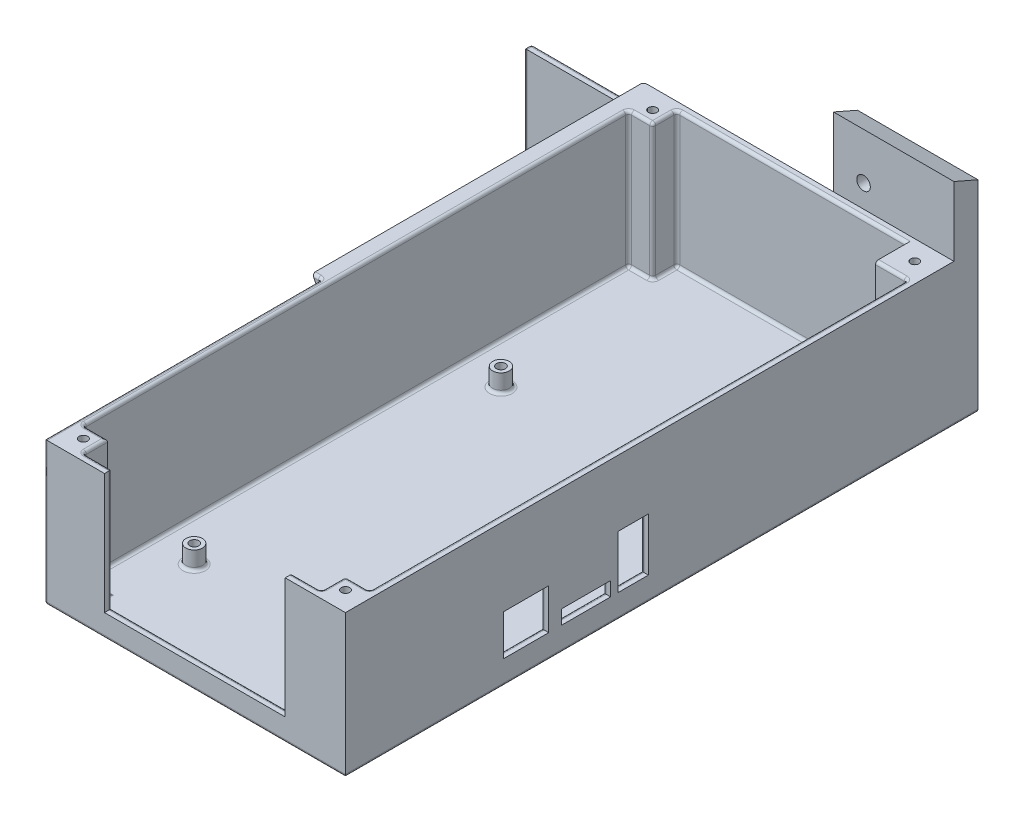
SolidWorks part; units mm, degrees
ref_plane "Front Plane" through (0, 0, 0) normal (0, 0, 1) x (1, 0, 0)
ref_plane "Top Plane" through (0, 0, 0) normal (0, 1, 0) x (1, 0, 0)
ref_plane "Right Plane" through (0, 0, 0) normal (1, 0, 0) x (0, 0, -1)
sketch "Sketch1" plane through (0, 0, 0) normal (0, 1, 0) x (1, 0, 0)
  line L0 (0, 0) -> (100, 0)
  line L2 (100, 210) -> (60, 210)
  line L3 (60, 210) -> (60, 202)
  line L4 (60, 202) -> (-40.25, 202)
  line L5 (-40.25, 202) -> (-40.25, 199.5)
  line L6 (-40.25, 199.5) -> (0, 199.5)
  line L7 (0, 199.5) -> (0, 0)
  line L8 (100, 210) -> (100, 202)
  line L14 (100, 202) -> (100, 0)
  point P11 (100, 200.922)
  dimension "D1" = 100
  dimension "D2" = 210
  dimension "D3" = 40
  dimension "D4" = 100.25
  dimension "D5" = 40.25
  dimension "D6" = 2.5
  dimension "D7" = 199.5
  dimension "D8" = 8
extrude "Boss-Extrude1" add sketch "Sketch1" along normal blind 47.5
sketch "Sketch2" plane through (0, 0, 0) normal (0, 1, 0) x (1, 0, 0)
  line L0 (2.5, 10.5) -> (10.5, 10.5)
  line L1 (10.5, 10.5) -> (10.5, 2.5)
  line L2 (10.5, 2.5) -> (89.5, 2.5)
  line L3 (89.5, 2.5) -> (89.5, 10.5)
  line L4 (89.5, 10.5) -> (97.5, 10.5)
  line L9 (10.5, 199.5) -> (10.5, 191.5)
  line L10 (10.5, 191.5) -> (2.5, 191.5)
  line L11 (2.5, 191.5) -> (2.5, 10.5)
  line L12 (0, 199.5) -> (0, 0) construction
  line L13 (60, 202) -> (-40.25, 202) construction
  line L15 (97.5, 189) -> (87, 189)
  line L16 (0, 0) -> (100, 0) construction
  line L17 (97.5, 10.5) -> (97.5, 189)
  line L22 (87, 189) -> (87, 199.5)
  line L24 (100, 0) -> (100, 210) construction
  line L25 (87, 199.5) -> (10.5, 199.5)
  dimension "D1" = 2.5
  dimension "D2" = 10.5
  dimension "D3" = 10.5
  dimension "D4" = 10.5
  dimension "D5" = 2.5
  dimension "D6" = 10.5
  dimension "D8" = 10.5
  dimension "D9" = 10.5
  dimension "D10" = 10.5
  dimension "D11" = 2.5
extrude "Cut-Extrude1" cut sketch "Sketch2" along normal blind 45 from offset 2.5
sketch "Sketch5" plane through (0, 47.5, 0) normal (0, 1, 0) x (1, 0, 0)
  line L1 (100, 210) -> (60, 210) construction
  line L2 (0, 0) -> (100, 0) construction
  line L3 (0, 199.5) -> (0, 0) construction
  line L4 (60, 202) -> (-40.25, 202) construction
  line L5 (100, 0) -> (100, 210) construction
  circle A0 centre (93.5, 195.5) radius 1.4
  circle A1 centre (93.5, 6.5) radius 1.4
  circle A2 centre (6.5, 6.5) radius 1.4
  circle A3 centre (6.5, 195.5) radius 1.4
  dimension "D1" = 2.8
  dimension "D4" = 2.8
  dimension "D9" = 2.8
  dimension "D2" = 2.8
  dimension "D3" = 14.5
  dimension "D5" = 6.5
  dimension "D6" = 6.5
  dimension "D7" = 6.5
  dimension "D8" = 6.5
  dimension "D10" = 6.5
  dimension "D11" = 6.5
extrude "Cut-Extrude2" cut sketch "Sketch5" against normal blind 10
sketch "Sketch6" plane through (0, 0, 0) normal (0, 0, 1) x (1, 0, 0)
  line L0 (0, 47.5) -> (100, 47.5) construction
  line L1 (20, 47.5) -> (80, 47.5)
  line L2 (20, 47.5) -> (20, 7.5)
  line L3 (20, 7.5) -> (80, 7.5)
  line L4 (80, 47.5) -> (80, 7.5)
  point P6 (50, 47.5)
  dimension "D1" = 40
  dimension "D2" = 60
extrude "Cut-Extrude3" cut sketch "Sketch6" against normal blind 10
sketch "Sketch7" plane through (0, 0, -199.5) normal (0, 0, 1) x (1, 0, 0)
  line L0 (-40.25, 47.5) -> (0, 47.5) construction
  line L2 (0, 47.5) -> (0, 0) construction
  circle A0 centre (-30.25, 10.5) radius 2.25
  circle A1 centre (-10.25, 30) radius 2.25
  dimension "D1" = 4.5
  dimension "D2" = 4.5
  dimension "D3" = 17.5
  dimension "D4" = 37
  dimension "D5" = 10.25
  dimension "D6" = 30.25
extrude "Cut-Extrude4" cut sketch "Sketch7" against normal blind 10
sketch "Sketch8" plane through (0, 2.5, 0) normal (0, 1, 0) x (1, 0, 0)
  line L0 (97.5, 10.5) -> (97.5, 189) construction
  line L2 (89.5, 10.5) -> (97.5, 10.5) construction
  line L3 (2.5, 10.5) -> (10.5, 10.5) construction
  circle A4 centre (15.95, 135.6737) radius 2.75
  circle A5 centre (15.95, 33.8237) radius 2.75
  circle A6 centre (92.25, 135.6737) radius 2.75
  circle A7 centre (92.25, 33.8237) radius 2.75
  circle A8 centre (15.95, 33.8237) radius 1.5
  circle A9 centre (92.25, 33.8237) radius 1.5
  circle A11 centre (15.95, 135.6737) radius 2.75
  circle A12 centre (15.95, 135.6737) radius 1.5
  circle A17 centre (92.25, 135.6737) radius 1.5
  dimension "D10" = 5.5
  dimension "D11" = 5.5
  dimension "D12" = 5.5
  dimension "D13" = 5.5
  dimension "D21" = 3
  dimension "D22" = 3
  dimension "D24" = 3
  dimension "D25" = 3
  dimension "D16" = 101.85
  dimension "D17" = 101.85
  dimension "D27" = 5.25
  dimension "D28" = 76.3
  dimension "D30" = 23.3237
  dimension "D31" = 23.3237
extrude "Boss-Extrude3" add sketch "Sketch8" along normal blind 6 contours A5 A8 | A7 A9 | A6 A17 | A4 A12
sketch "Sketch9" plane through (0, 47.5, 0) normal (0, 1, 0) x (1, 0, 0)
  line L1 (60, 210) -> (100, 210)
  line L2 (60, 210) -> (60, 202)
  line L3 (60, 202) -> (100, 202)
  line L4 (100, 210) -> (100, 202)
extrude "Boss-Extrude4" add sketch "Sketch9" along normal blind 15
sketch "Sketch10" plane through (0, 0, -210) normal (0, 0, -1) x (-1, 0, 0)
  line L0 (-100, 62.5) -> (-60, 62.5) construction
  line L1 (-60, 62.5) -> (-60, 0) construction
  line L2 (-60, 47.5) -> (-60, 0) construction
  circle A0 centre (-70, 55) radius 2.25
  circle A1 centre (-90, 35) radius 2.25
  dimension "D3" = 4.5
  dimension "D4" = 4.5
  dimension "D1" = 7.5
  dimension "D2" = 27.5
  dimension "D5" = 10
  dimension "D6" = 30
extrude "Cut-Extrude5" cut sketch "Sketch10" against normal blind 8
sketch "Sketch11" plane through (97.5, 0, 0) normal (-1, 0, 0) x (0, 0, 1)
  line L1 (-52.4737, 8) -> (-67.4737, 8)
  line L2 (-52.4737, 8) -> (-52.4737, 21.5)
  line L3 (-52.4737, 21.5) -> (-67.4737, 21.5)
  line L4 (-67.4737, 8) -> (-67.4737, 21.5)
  line L6 (-31.0737, 8.5) -> (-36.5737, 8.5) construction
  line L7 (-90.5637, 25.6) -> (-100.5637, 25.6)
  line L8 (-33.8237, 8.5) -> (-52.4737, 8.5) construction
  line L9 (-90.5637, 25.6) -> (-90.5637, 8)
  line L10 (-71.7437, 12.7) -> (-88.0437, 12.7)
  line L11 (-71.7437, 12.7) -> (-71.7437, 8)
  line L12 (-71.7437, 8) -> (-88.0437, 8)
  line L13 (-88.0437, 12.7) -> (-88.0437, 8)
  line L14 (-90.5637, 8) -> (-100.5637, 8)
  line L15 (-100.5637, 25.6) -> (-100.5637, 8)
  dimension "D2" = 4.27
  dimension "D3" = 15
  dimension "D4" = 13.5
  dimension "D5" = 18.65
  dimension "D6" = 4.7
  dimension "D7" = 16.3
  dimension "D9" = 10
  dimension "D10" = 2.52
  dimension "D11" = 17.6
extrude "Cut-Extrude6" cut sketch "Sketch11" against normal blind 8
sketch "Sketch12" plane through (0, 0, 0) normal (0, 0, 1) x (1, 0, 0)
  line L0 (0, 12.06) -> (-3.13, 12.06)
  line L1 (0, 47.5) -> (0, 0) construction
  line L2 (-3.13, 12.06) -> (-3.13, 14.05)
  line L3 (-3.13, 14.05) -> (-5.8153, 12.255)
  line L4 (-5.8153, 12.255) -> (-5.8153, 6.305)
  line L5 (-5.8153, 6.305) -> (-3.13, 4.51)
  line L6 (-3.13, 4.51) -> (-3.13, 6.5)
  line L7 (-3.13, 6.5) -> (0, 6.5)
  line L8 (0, 6.5) -> (0, 12.06)
  line L9 (-40.25, 0) -> (0, 0) construction
  line L10 (-7.511, 19.28) -> (7.333, 19.28) construction
  line L11 (-3.13, 32.06) -> (0, 32.06)
  line L12 (-3.13, 34.05) -> (-3.13, 32.06)
  line L13 (-5.8153, 32.255) -> (-3.13, 34.05)
  line L14 (-5.8153, 26.305) -> (-5.8153, 32.255)
  line L15 (-3.13, 24.51) -> (-5.8153, 26.305)
  line L16 (-3.13, 26.5) -> (-3.13, 24.51)
  line L17 (0, 26.5) -> (-3.13, 26.5)
  line L18 (0, 32.06) -> (0, 26.5)
  dimension "D1" = 5.56
  dimension "D2" = 3.13
  dimension "D3" = 3.13
  dimension "D4" = 1.99
  dimension "D5" = 1.99
  dimension "D6" = 3.23
  dimension "D7" = 5.95
  dimension "D8" = 3.23
  dimension "D9" = 6.5
  dimension "D10" = 7.22
extrude "Boss-Extrude5" add sketch "Sketch12" against normal blind 50 from offset 80 offset against normal yes
sketch "Sketch15" plane through (0, 0, -199.5) normal (0, 0, 1) x (1, 0, 0)
  line L0 (0, 47.5) -> (0, 0) construction
  line L1 (-40.25, 47.5) -> (0, 47.5)
  line L2 (-40.25, 47.5) -> (-40.25, 40)
  line L3 (-40.25, 40) -> (0, 40)
  line L4 (0, 47.5) -> (0, 40)
  dimension "D1" = 7.5
extrude "Cut-Extrude7" cut sketch "Sketch15" against normal blind 10 contours L2 L1 L4 L3
sketch "Sketch16" plane through (0, 0, -202) normal (0, 0, 1) x (1, 0, 0)
  line L0 (0, 41.5) -> (-3, 47.5)
  line L3 (-3, 47.5) -> (0, 47.5)
  line L4 (0, 47.5) -> (0, 41.5)
  point P2 (0, 0)
  point P3 (-1, 46.5)
  point P4 (0, 0)
  dimension "D1" = 3
  dimension "D2" = 6
extrude "Boss-Extrude6" add sketch "Sketch16" along normal blind 110
sketch "Sketch18" plane through (100, 0, 0) normal (1, 0, 0) x (0, 0, -1)
  line L0 (202, 62.5) -> (202, 70.45)
  line L1 (210, 62.5) -> (210, 66.95)
  line L2 (202, 70.45) -> (210, 66.95)
  line L3 (202, 62.5) -> (210, 62.5)
  dimension "D1" = 7.95
  dimension "D2" = 4.45
extrude "Boss-Extrude7" add sketch "Sketch18" against normal up to surface (40 mm away) up to face at (60, 34.5, -205.2)
fillet "Fillet1" radius 1 81 edges at (10.5, 47.5, -6.5) (6.5, 47.5, -10.5) (6.5, 47.5, -191.5) (15.25, 47.5, -2.5) (10.5, 25, -2.5) (84.75, 47.5, -2.5) (80, 27.5, -2.5) (50, 7.5, -2.5) (20, 27.5, -2.5) (89.5, 47.5, -6.5) (89.5, 25, -2.5) (93.5, 47.5, -10.5) (89.5, 25, -10.5) (97.5, 47.5, -99.75) (97.5, 25, -10.5) (97.5, 25.6, -95.5637) (97.5, 16.8, -100.5637) (97.5, 8, -95.5637) (97.5, 16.8, -90.5637) (97.5, 12.7, -79.8937) (97.5, 10.35, -88.0437) (97.5, 8, -79.8937) (97.5, 10.35, -71.7437) (97.5, 21.5, -59.9737) (97.5, 14.75, -67.4737) (97.5, 8, -59.9737) (97.5, 14.75, -52.4737) (10.5, 25, -191.5) (10.5, 47.5, -195.5) (2.5, 25, -10.5) (2.5, 47.5, -101) (2.5, 25, -191.5) (6.5, 2.5, -191.5) (10.5, 2.5, -195.5) (97.5, 2.5, -99.75) (93.5, 2.5, -10.5) (89.5, 2.5, -6.5) (50, 2.5, -2.5) (10.5, 2.5, -6.5) (6.5, 2.5, -10.5) (2.5, 2.5, -101) (15.95, 2.5, -31.0737) (92.25, 2.5, -31.0737) (92.25, 2.5, -132.9237) (15.95, 2.5, -132.9237) (50, 0, 0) (100, 0, -105) (80, 0, -210) (60, 0, -206) (9.875, 0, -202) (-40.25, 0, -200.75) (-20.125, 0, -199.5) (0, 0, -99.75) (0, 26.5, -105) (0, 29.28, -80) (0, 32.06, -105) (0, 29.28, -130) (0, 20, -199.5) (0, 47.5, -46) (0, 23.75, 0) (0, 6.5, -105) (0, 9.28, -80) (0, 12.06, -105) (0, 9.28, -130) (92.25, 47.5, -189) (48.75, 47.5, -199.5) (97.5, 25, -189) (10.5, 25, -199.5) (48.75, 2.5, -199.5) (87, 2.5, -194.25) (92.25, 2.5, -189) (-1.5, 47.5, -92) (-20.125, 40, -202) (-1.5, 44.5, -202) (-40.25, 20, -202) (-40.25, 40, -200.75) (-40.25, 20, -199.5) (0, 44.5, -92) (0, 40, -200.75) (0, 40.75, -202) (0, 41.5, -147)
